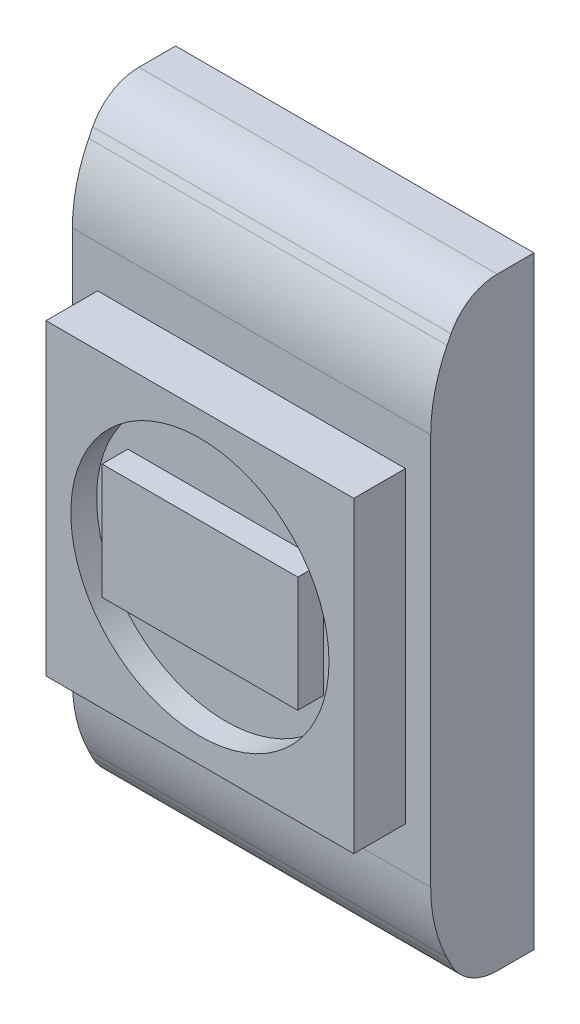
SolidWorks part; units mm, degrees
note: The reader was unsure of these and kept them because the rebuilt part matched: shared geometry of "Sketch1<4>", "Sketch8<3>".
ref_plane "Front Plane" through (0, 0, 0) normal (0, 0, 1) x (1, 0, 0)
ref_plane "Top Plane" through (0, 0, 0) normal (0, 1, 0) x (1, 0, 0)
ref_plane "Right Plane" through (0, 0, 0) normal (1, 0, 0) x (0, 0, -1)
sketch "Sketch1" plane through (0, 0, 0) normal (0, 0, 1) x (1, 0, 0)
  line L1 (-3.47, 6) -> (3.47, 6)
  line L2 (-3.47, 6) -> (-3.47, -6)
  line L3 (-3.47, -6) -> (3.47, -6)
  line L4 (3.47, 6) -> (3.47, -6)
  line L5 (-3.47, 6) -> (3.47, -6) construction
  line L6 (-3.47, -6) -> (3.47, 6) construction
  line L7 (-2.98, 2.98) -> (2.98, 2.98)
  line L8 (-2.98, 2.98) -> (-2.98, -2.98)
  line L9 (-2.98, -2.98) -> (2.98, -2.98)
  line L10 (2.98, 2.98) -> (2.98, -2.98)
  line L11 (-2.98, 2.98) -> (2.98, -2.98) construction
  line L12 (-2.98, -2.98) -> (2.98, 2.98) construction
  line L13 (-3.47, 4.5) -> (3.47, 4.5)
  line L14 (-3.47, 4.5) -> (-3.47, -4.5)
  line L15 (-3.47, -4.5) -> (3.47, -4.5)
  line L16 (3.47, 4.5) -> (3.47, -4.5)
  line L17 (-3.47, 4.5) -> (3.47, -4.5) construction
  line L18 (-3.47, -4.5) -> (3.47, 4.5) construction
  point P0 (0, 0)
  point P5 (0, 0)
  point P11 (0, 0)
  dimension "D1" = 12
  dimension "D2" = 6.94
  dimension "D3" = 5.96
  dimension "D4" = 5.96
  dimension "D5" = 9
sketch "Sketch2" plane through (0, 0, 0) normal (1, 0, 0) x (0, 0, -1)
  line L0 (0, 4.5) -> (0.7288, 5.9578)
  line L1 (0, 4.5) -> (0, -4.5) construction
  line L2 (0, 4.5) -> (0, -4.5) construction
  line L3 (0, 6) -> (0, -6) construction
  dimension "D1" = 26.56
ref_plane "Plane1" through (0, 0.8997, 1.7998) normal (0, -0.4471, -0.8945) x (-1, 0, 0)
sketch "Sketch3" plane through (0, 0.8997, 1.7998) normal (0, -0.4471, -0.8945) x (-1, 0, 0)
  line L0 (3.47, 4.0251) -> (-3.47, 4.0251)
  line L1 (3.47, 4.0251) -> (3.47, 5.5251)
  line L2 (-3.47, 4.0251) -> (-3.47, 5.5251)
  line L3 (3.47, 5.5251) -> (-3.47, 5.5251)
  dimension "D1" = 1.5
sketch "Sketch4" plane through (0, 0, 0) normal (1, 0, 0) x (0, 0, -1)
  line L0 (0, -4.5) -> (0.8284, -6.179)
  line L1 (0, -4.5) -> (0, 4.5) construction
  line L2 (0, -6) -> (0, 6) construction
  dimension "D1" = 26.26
ref_plane "Plane2" through (0, -0.8809, 1.7855) normal (0, -0.4424, 0.8968) x (1, 0, 0)
sketch "Sketch5" plane through (0, -0.8809, 1.7855) normal (0, -0.4424, 0.8968) x (1, 0, 0)
  line L0 (-3.47, -4.0356) -> (3.47, -4.0356)
  line L1 (-3.47, -4.0356) -> (-3.47, -5.5356)
  line L2 (3.47, -4.0356) -> (3.47, -5.5356)
  line L3 (-3.47, -5.5356) -> (3.47, -5.5356)
  dimension "D1" = 1.5
extrude "Boss-Extrude1" add sketch "Sketch1" against normal blind 2 contours L13 L16 L15 L14
extrude "Boss-Extrude2" add sketch "Sketch3" along normal blind 1
extrude "Boss-Extrude3" add sketch "Sketch5" against normal blind 1
ref_plane "Plane3" through (-3.47, 0, 0) normal (-1, 0, 0) x (0, 0, 1)
sketch "Sketch7" plane through (-3.47, 0, 0) normal (-1, 0, 0) x (0, 0, 1)
  line L0 (-2, 4.5) -> (-1.118, 4.5)
  line L1 (-1.118, 4.5) -> (-1.5652, 5.3946)
  line L2 (-1.5652, 5.3946) -> (-0.6707, 5.8417)
  line L3 (-0.6707, 5.8417) -> (-2, 5.8417)
  line L4 (-2, 5.8417) -> (-2, 4.5)
  line L5 (-2, -4.5) -> (-1.1151, -4.5)
  line L6 (-1.1151, -4.5) -> (-1.5605, -5.4027)
  line L7 (-1.5605, -5.4027) -> (-0.6637, -5.8452)
  line L8 (-0.6637, -5.8452) -> (-2, -5.8452)
  line L9 (-2, -5.8452) -> (-2, -4.5)
extrude "Boss-Extrude4" add sketch "Sketch7" against normal up to surface (6.94 mm away) up to face at (3.47, -0.0012, -1.0693)
fillet "Fillet4" radius 3 1 edges at (0, -4.5, 0)
fillet "Fillet5" radius 1 1 edges at (0, -5.8452, -0.6637)
fillet "Fillet6" radius 3 1 edges at (0, 4.5, 0)
fillet "Fillet7" radius 1 1 edges at (0, 5.8417, -0.6707)
extrude "Boss-Extrude5" add sketch "Sketch1<4>" along normal blind 1 contours L7 L10 L9 L8
sketch "Sketch1<4>" plane through (0, 0, 0) normal (0, 0, 1) x (1, 0, 0) same geometry as "Sketch1"
ref_plane "Plane4" through (0, 0, 1) normal (0, 0, 1) x (1, 0, 0)
sketch "Sketch8" plane through (0, 0, 1) normal (0, 0, 1) x (1, 0, 0)
  line L1 (-1.8958, -1.1175) -> (1.8958, -1.1175)
  line L2 (-1.8958, -1.1175) -> (-1.8958, 1.1175)
  line L3 (-1.8958, 1.1175) -> (1.8958, 1.1175)
  line L4 (1.8958, -1.1175) -> (1.8958, 1.1175)
  line L5 (-1.8958, -1.1175) -> (1.8958, 1.1175) construction
  line L6 (-1.8958, 1.1175) -> (1.8958, -1.1175) construction
  circle A0 centre (0, 0) radius 2.5
extrude "Cut-Extrude1" cut sketch "Sketch8" against normal blind 0.5 contours A0
extrude "Boss-Extrude6" add sketch "Sketch8<3>" against normal blind 0.5 contours L3 L4 L1 L2
sketch "Sketch8<3>" plane through (0, 0, 1) normal (0, 0, 1) x (1, 0, 0) same geometry as "Sketch8"
